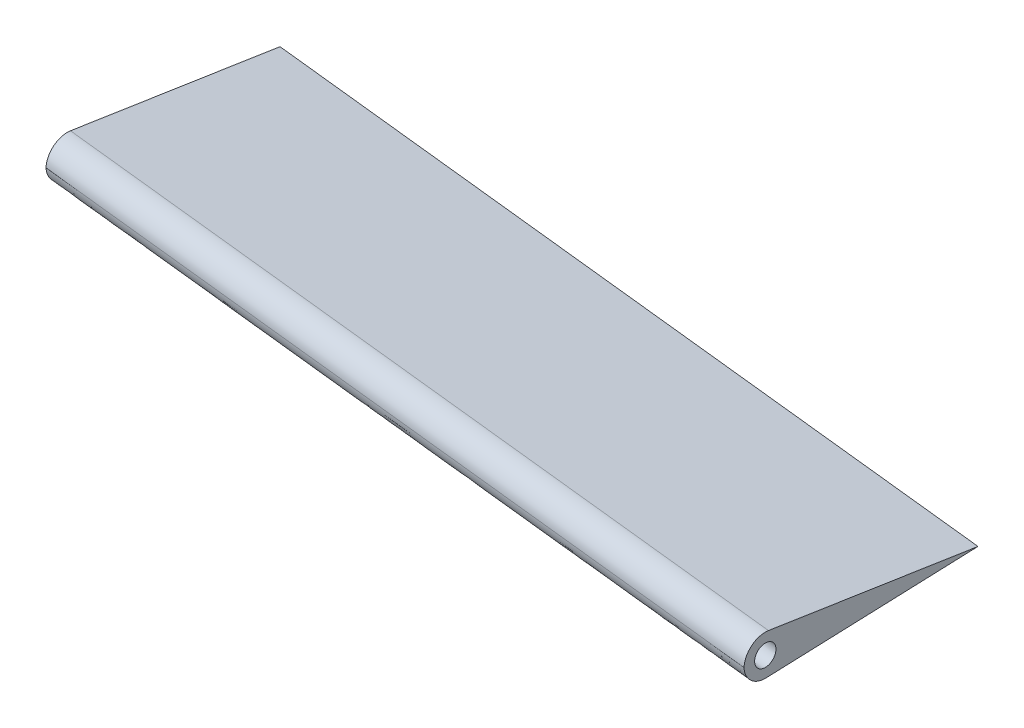
SolidWorks part; units mm, degrees
material "PET"
ref_plane "Alzado" through (0, 0, 0) normal (0, 0, 1) x (1, 0, 0)
ref_plane "Planta" through (0, 0, 0) normal (0, 1, 0) x (1, 0, 0)
ref_plane "Vista lateral" through (0, 0, 0) normal (1, 0, 0) x (0, 0, -1)
ref_plane "Plano2" through (184.57, 0, 0) normal (1, 0, 0) x (0, 0, -1)
sketch "Croquis11" plane through (0, 0, 0) normal (1, 0, 0) x (0, 0, -1)
  line L0 (-27.625, 5.2383) -> (27.625, -3.1759)
  line L1 (27.625, -3.1759) -> (-27.625, -5.2383)
  line L2 (-27.625, -5.2383) -> (-27.625, 5.2383)
  dimension "D1" = 10.4766
  dimension "D2" = 55.887
  dimension "D3" = 55.2885
sketch "Croquis12" plane through (184.57, 0, 0) normal (1, 0, 0) x (0, 0, -1)
  line L0 (-47.415, 5.2383) -> (7.835, -3.1759)
  line L1 (7.835, -3.1759) -> (-47.415, -5.2417)
  line L2 (-47.415, -5.2417) -> (-47.415, 5.2383)
  line L3 (-27.625, 5.2383) -> (-48.4234, 5.2383) construction
  dimension "D1" = 19.79
  dimension "D2" = 10.48
  dimension "D3" = 55.887
loft "Recubrir2" add profiles "Croquis12", "Croquis11"
fillet "Redondeo2" radius 5 2 edges
ref_plane "Plano3" through (0, 4.3565, 21.835) normal (0.9943, 0, 0.1066) x (0.1066, 0, -0.9943)
sketch "Croquis13" plane through (2.3279, 0, 0.1244) normal (0.9943, 0, 0.1066) x (0.1066, 0, -0.9943)
  circle A0 centre (-22.5847, -0.3147) radius 2.5
  point P0 (0, 0)
  point P6 (0, 0)
  point P8 (-15.5942, 6.5269)
  dimension "D1" = 5
  dimension "D2" = 4.7319
extrude "Cortar-Extruir1" cut sketch "Croquis13" against normal through all both and the other way through all
